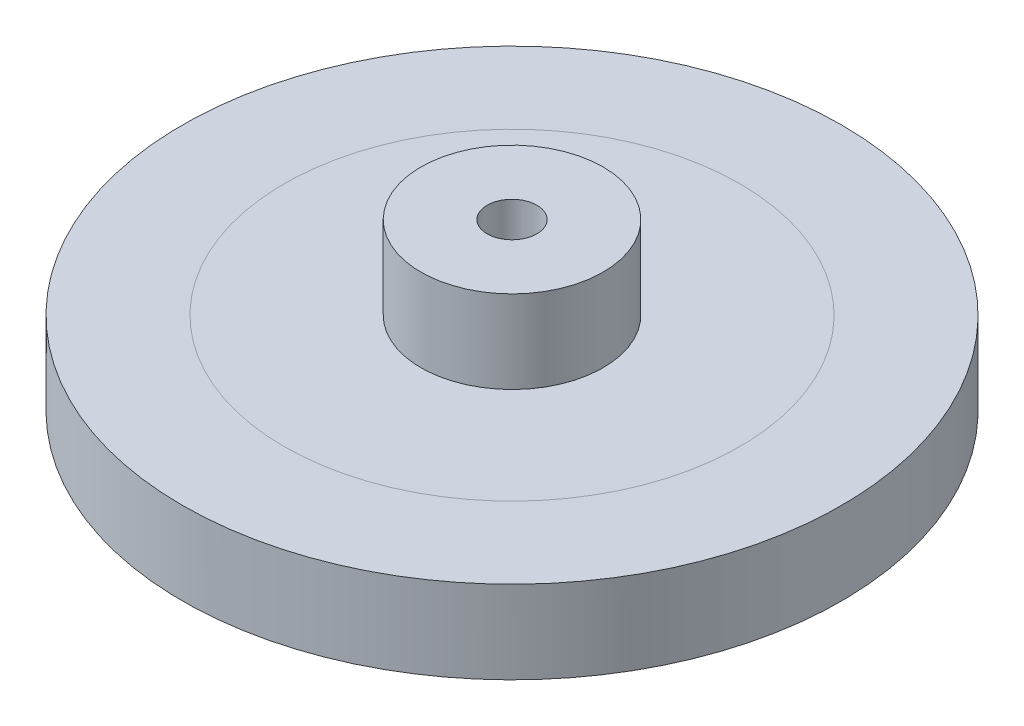
SolidWorks part; units mm, degrees
material "6061 Alloy"
ref_plane "Front Plane" through (0, 0, 0) normal (0, 0, 1) x (1, 0, 0)
ref_plane "Top Plane" through (0, 0, 0) normal (0, 1, 0) x (1, 0, 0)
ref_plane "Right Plane" through (0, 0, 0) normal (1, 0, 0) x (0, 0, -1)
sketch "Sketch1" plane through (0, 0, 0) normal (0, 0, 1) x (1, 0, 0)
  line L0 (0, 0) -> (0, 20) construction
  line L1 (0, 20) -> (3, 20) construction
  line L2 (0, 0) -> (3, 0) construction
  line L3 (3, 20) -> (3, 0)
  line L4 (3, 20) -> (11, 20)
  line L5 (11, 20) -> (11, 10)
  line L6 (11, 10) -> (27.5, 10)
  line L7 (27.5, 10) -> (27.5, 0)
  line L8 (27.5, 0) -> (3, 0)
  dimension "D1" = 22
  dimension "D2" = 10
  dimension "D3" = 6
  dimension "D4" = 55
revolve "Revolve1" add sketch "Sketch1" angle 360 about L0
sketch "Sketch2" plane through (0, 0, 0) normal (0, -1, 0) x (1, 0, 0)
  circle A0 centre (0, 0) radius 39.7887
  circle A1 centre (0, 0) radius 27.5 construction
  circle A2 centre (0, 0) radius 27.5
  dimension "D1" = 79.5775
extrude "Boss-Extrude1" add sketch "Sketch2" against normal up to surface (10 mm away) separate body up to face at (0, 10, -11)
